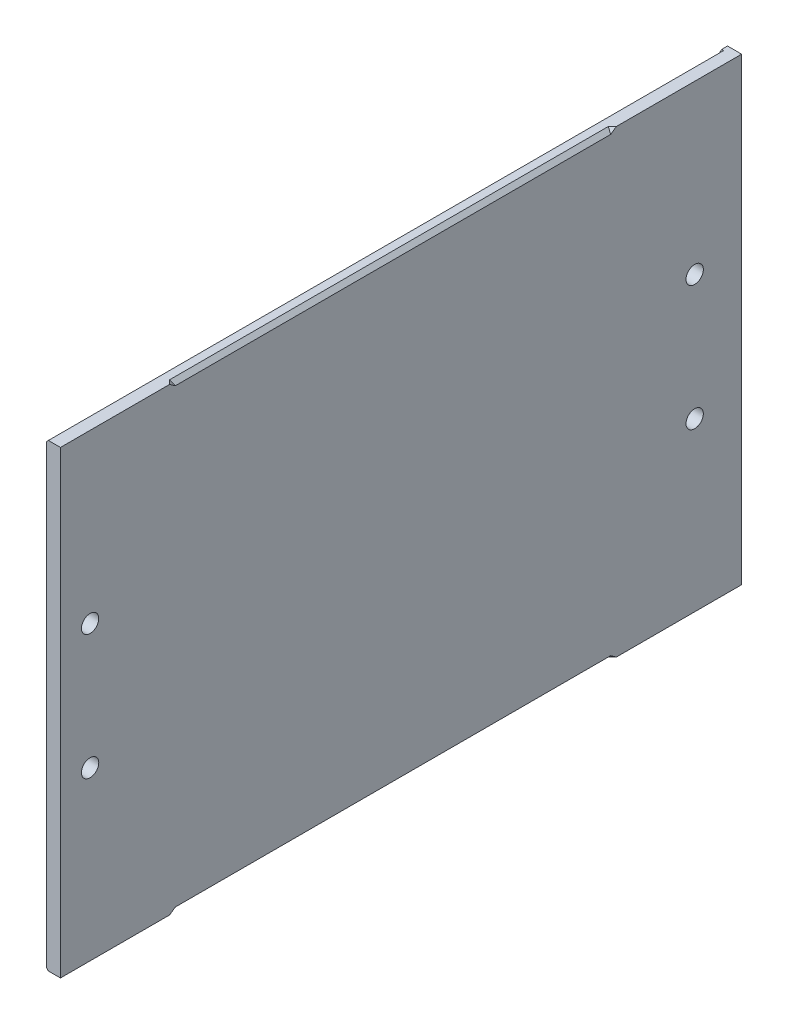
SolidWorks part; units mm, degrees
ref_plane "Front Plane" through (0, 0, 0) normal (0, 0, 1) x (1, 0, 0)
ref_plane "Top Plane" through (0, 0, 0) normal (0, 1, 0) x (1, 0, 0)
ref_plane "Right Plane" through (0, 0, 0) normal (1, 0, 0) x (0, 0, -1)
sketch "Sketch1" plane through (0, 0, 0) normal (0, 0, 1) x (1, 0, 0)
  line L1 (0, 0) -> (134, 0)
  line L2 (0, 0) -> (0, 57)
  line L3 (0, 57) -> (134, 57)
  line L4 (134, 0) -> (134, 57)
  dimension "D1" = 134
  dimension "D2" = 57
extrude "Boss-Extrude1" add sketch "Sketch1" along normal blind 250
sketch "Sketch2" plane through (0, 0, 250) normal (0, 0, 1) x (1, 0, 0)
  line L0 (0, 57) -> (0, 0) construction
  line L1 (9.5, 53.5) -> (124.5, 53.5)
  line L2 (9.5, 53.5) -> (9.5, 0)
  line L3 (9.5, 0) -> (124.5, 0)
  line L4 (124.5, 53.5) -> (124.5, 0)
  line L5 (134, 57) -> (0, 57) construction
  line L6 (134, 0) -> (134, 57) construction
  line L8 (0, 0) -> (134, 0) construction
  dimension "D1" = 9.5
  dimension "D2" = 3.5
  dimension "D3" = 9.5
extrude "Cut-Extrude1" cut sketch "Sketch2" against normal blind 246.5
sketch "Sketch3" plane through (0, 57, 0) normal (0, 1, 0) x (1, 0, 0)
  line L0 (134, -250) -> (0, -250) construction
  line L1 (9.5, -250) -> (124.5, -250)
  line L2 (9.5, -250) -> (9.5, -56)
  line L3 (9.5, -56) -> (124.5, -56)
  line L4 (124.5, -250) -> (124.5, -56)
  line L5 (0, -250) -> (0, 0) construction
  line L6 (134, -250) -> (134, 0) construction
  dimension "D1" = 9.5
  dimension "D2" = 9.5
  dimension "D3" = 194
extrude "Cut-Extrude2" cut sketch "Sketch3" against normal up to surface (3.5 mm away) up to face at (67, 53.5, 126.75)
sketch "Sketch4" plane through (0, 0, 0) normal (0, -1, 0) x (1, 0, 0)
  line L0 (67, 250) -> (67, 0) construction
  line L1 (0, 250) -> (9.5, 250) construction
  line L2 (9.5, 0) -> (124.5, 0) construction
  line L3 (0, 250) -> (0, 0) construction
  line L4 (0, 202.5) -> (6, 202.5)
  line L5 (0, 202.5) -> (0, 82.5)
  line L6 (0, 82.5) -> (6, 82.5)
  line L7 (6, 202.5) -> (6, 82.5)
  line L8 (128, 202.5) -> (128, 82.5)
  line L9 (134, 82.5) -> (128, 82.5)
  line L10 (134, 202.5) -> (134, 82.5)
  line L11 (134, 202.5) -> (128, 202.5)
  line L13 (0, 250) -> (9.5, 250) construction
  dimension "D1" = 47.5
  dimension "D2" = 6
  dimension "D3" = 120
extrude "Cut-Extrude3" cut sketch "Sketch4" against normal through all
chamfer "Chamfer1" distance 6 angle 45 4 edges at (6, 28.5, 202.5) (6, 28.5, 82.5) (128, 28.5, 82.5) (128, 28.5, 202.5)
sketch "Sketch5" plane through (134, 0, 0) normal (1, 0, 0) x (0, 0, -1)
  line L0 (-250, 15.5) -> (0, 15.5) construction
  line L4 (-250, 0) -> (-250, 57) construction
  line L5 (0, 0) -> (0, 57) construction
  line L6 (-250, 57) -> (-202.5, 57) construction
  circle A0 centre (-217.65, 15.5) radius 2.15
  circle A1 centre (-67.65, 15.5) radius 2.15
  dimension "D2" = 4.3
  dimension "D4" = 150
  dimension "D1" = 41.5
  dimension "D3" = 32.35
extrude "Cut-Extrude4" cut sketch "Sketch5" against normal blind 134
sketch "Sketch6" plane through (9.5, 0, 0) normal (1, 0, 0) x (0, 0, -1)
  line L0 (-56, 57) -> (-250, 57) construction
  line L1 (-250, 0) -> (-225, 0)
  line L2 (-250, 0) -> (-250, 4.5)
  line L3 (-250, 4.5) -> (-225, 4.5)
  line L4 (-225, 0) -> (-225, 4.5)
  dimension "D1" = 52.5
  dimension "D2" = 25
extrude "Boss-Extrude2" add sketch "Sketch6" along normal blind 115
sketch "Sketch7" plane through (134, 0, 0) normal (1, 0, 0) x (0, 0, -1)
  circle A0 centre (-217.65, 15.5) radius 3.65
  circle A1 centre (-67.65, 15.5) radius 3.65
  dimension "D1" = 7.3
extrude "Cut-Extrude5" cut sketch "Sketch7" against normal blind 3.6
sketch "Sketch8" plane through (0, 0, 0) normal (-1, 0, 0) x (0, 0, 1)
  circle A0 centre (217.65, 15.5) radius 3.65
  circle A1 centre (67.65, 15.5) radius 3.65
  dimension "D1" = 7.3
extrude "Cut-Extrude6" cut sketch "Sketch8" against normal blind 3.6
mirror "Mirror1" about plane through (0, 0, 0) normal (0, 1, 0) of "Cut-Extrude6", "Cut-Extrude5", "Boss-Extrude2", "Cut-Extrude4", "Chamfer1", "Cut-Extrude3", "Cut-Extrude2", "Cut-Extrude1", "Boss-Extrude1"
sketch "Sketch9" plane through (0, 0, 250) normal (0, 0, 1) x (1, 0, 0)
  line L0 (0, 0) -> (134, 0) construction
  line L1 (0, 57) -> (0, -57) construction
  line L2 (134, -57) -> (134, 57) construction
  circle A0 centre (25, 0) radius 1.65
  circle A1 centre (109, 0) radius 1.65
  dimension "D1" = 3.3
  dimension "D2" = 25
  dimension "D3" = 25
extrude "Cut-Extrude7" cut sketch "Sketch9" against normal blind 25
chamfer "Chamfer2" distance 1 angle 45 24 edges at (0, -57, 226.25) (3, -57, 199.5) (6, -57, 142.5) (3, -57, 85.5) (0, 57, 226.25) (3, 57, 199.5) (6, 57, 142.5) (3, 57, 85.5) (134, 57, 226.25) (131, 57, 199.5) (128, 57, 142.5) (131, 57, 85.5) (134, -57, 226.25) (131, -57, 199.5) (128, -57, 142.5) (131, -57, 85.5) (134, -57, 41.25) (67, -57, 0) (134, 0, 0) (134, 57, 41.25) (67, 57, 0) (0, -57, 41.25) (0, 0, 0) (0, 57, 41.25)
chamfer "Chamfer3" distance 0.5 angle 45 8 edges at (134, 15.5, 64) (134, -15.5, 64) (134, 15.5, 214) (134, -15.5, 214) (0, 15.5, 221.3) (0, -15.5, 221.3) (0, -15.5, 71.3) (0, 15.5, 71.3)
sketch "Sketch11" plane through (0, 57, 0) normal (0, 1, 0) x (1, 0, 0)
  line L0 (128, -88.5) -> (128, -56)
  line L1 (128, -56) -> (124.5, -56)
  line L2 (124.5, -56) -> (9.5, -56) construction
  line L3 (128, -88.5) -> (134, -88.5)
  line L4 (134, -88.5) -> (134, 0)
  line L5 (134, 0) -> (0, 0)
  line L6 (0, 0) -> (0, -250)
  line L7 (0, -250) -> (134, -250)
  line L8 (134, -250) -> (134, -196.5)
  line L9 (134, -196.5) -> (128, -196.5)
  line L10 (128, -196.5) -> (128, -225)
  line L11 (128, -225) -> (124.5, -225)
  line L12 (124.5, -250) -> (124.5, -56) construction
  line L13 (124.5, -225) -> (124.5, -56)
  line L14 (124.5, -225) -> (9.5, -225) construction
  line L15 (134, -202.5) -> (134, -250) construction
  line L16 (0, -250) -> (0, -202.5) construction
  line L17 (124.5, -250) -> (9.5, -250) construction
  line L18 (134, -1) -> (134, -82.5) construction
  line L19 (1, 0) -> (133, 0) construction
extrude "Cut-Extrude9" cut sketch "Sketch11" against normal through all
chamfer "Chamfer4" distance 0.5 angle 45 2 edges at (124.5, -57, 140.5) (124.5, 57, 140.5)
sketch "Sketch12" plane through (0, 57, 0) normal (0, 1, 0) x (1, 0, 0)
  line L0 (125, -56) -> (125, -225) construction
  line L1 (124.5, -56) -> (125, -56)
  line L2 (124.5, -56) -> (124.5, -58)
  line L3 (124.5, -58) -> (125, -58)
  line L4 (125, -56) -> (125, -58)
  dimension "D1" = 2
extrude "Boss-Extrude3" add sketch "Sketch12" against normal up to surface (114 mm away) up to face at (127, -57, 141.5)
chamfer "Chamfer5" distance 0.5 angle 45 2 edges at (124.75, 57, 58) (124.75, -57, 58)
